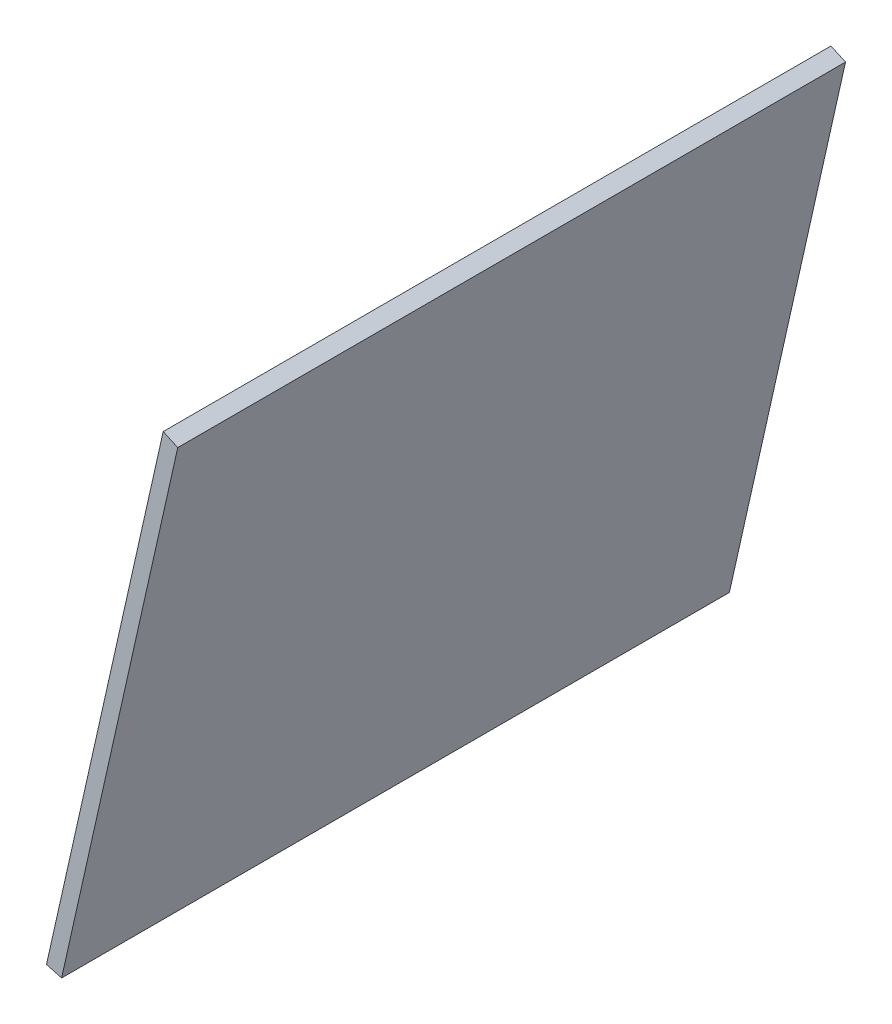
SolidWorks part; units mm, degrees
material "Pine"
ref_plane "Front Plane" through (0, 0, 0) normal (0, 0, 1) x (1, 0, 0)
ref_plane "Top Plane" through (0, 0, 0) normal (0, 1, 0) x (1, 0, 0)
ref_plane "Right Plane" through (0, 0, 0) normal (1, 0, 0) x (0, 0, -1)
sketch "Sketch1" plane through (0, 0, 0) normal (0, 0, 1) x (1, 0, 0)
  line L0 (-615.4529, 1612.4067) -> (-756.8391, 982.5955) construction
  line L12 (-596.8655, 1608.234) -> (-738.2517, 978.4228)
  line L13 (-756.6614, 983.3872) -> (-738.2517, 978.4228)
  line L26 (-614.5819, 1616.2869) -> (-596.8655, 1608.234)
  line L63 (-614.5819, 1616.2869) -> (-756.6614, 983.3872)
  dimension "D7" = 19.05
extrude "Boss-Extrude1" add sketch "Sketch1" along normal blind 812.8
